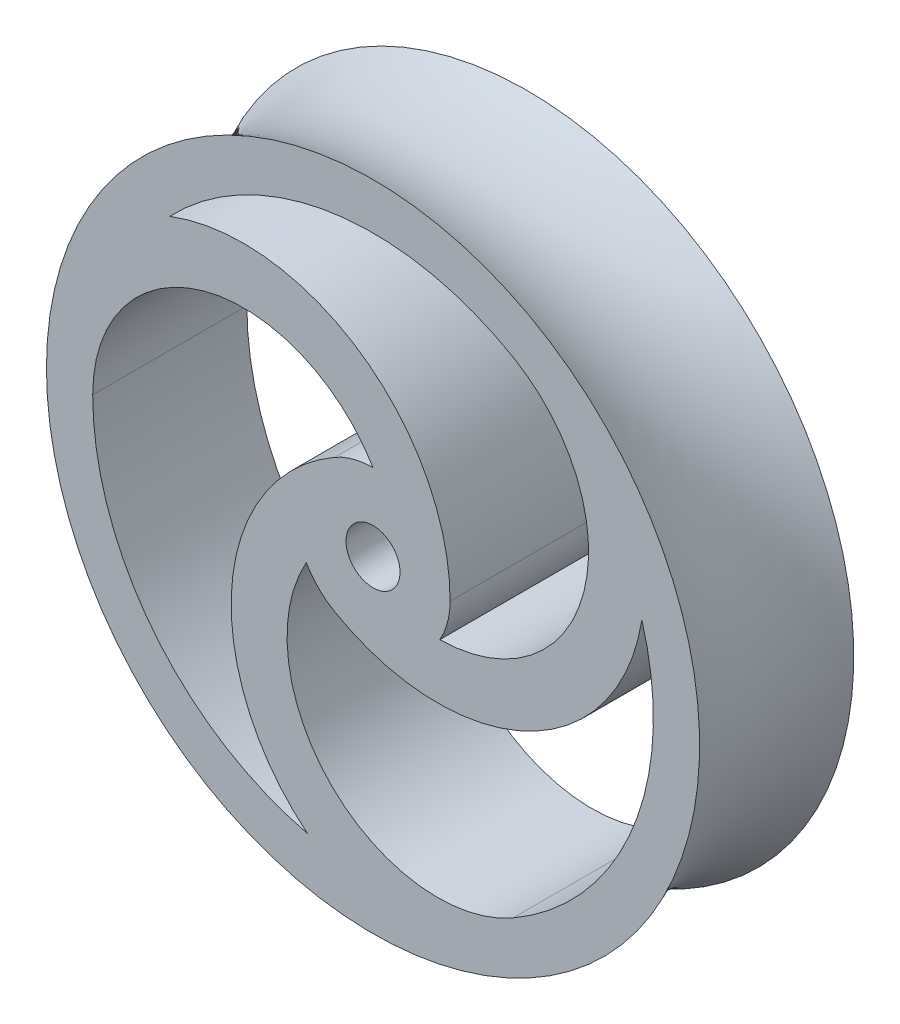
SolidWorks part; units mm, degrees
ref_plane "Front Plane" through (0, 0, 0) normal (0, 0, 1) x (1, 0, 0)
ref_plane "Top Plane" through (0, 0, 0) normal (0, 1, 0) x (1, 0, 0)
ref_plane "Right Plane" through (0, 0, 0) normal (1, 0, 0) x (0, 0, -1)
sketch "Sketch2" plane through (0, 0, 0) normal (0, 1, 0) x (1, 0, 0)
  line L0 (0, 5) -> (0, -5)
  line L1 (0, 5) -> (21.1839, 5)
  line L2 (0, -5) -> (21.1839, -5)
  line L3 (0, 0) -> (20, 0) construction
  arc A0 (21.1839, 5) -> (21.1839, -5) centre (31.15, 0) ccw
  point P4 (0, 0)
  point P9 (26.8135, 5)
  point P10 (26.8135, -5)
  point P11 (20, 0)
  point P12 (27.961, 5)
  dimension "D3" = 11.15
  dimension "D1" = 10
  dimension "D2" = 20
revolve "Revolve1" add sketch "Sketch2" angle 360 about L0
sketch "Sketch3" plane through (0, 0, -5) normal (0, 0, -1) x (-1, 0, 0)
  line L0 (0, 0) -> (0, 21.1839) construction
  line L1 (0, 0) -> (18.1839, 0) construction
  circle A0 centre (0, 0) radius 1.75
  circle A1 centre (0, 0) radius 18.1839 construction
  circle A2 centre (0, 0) radius 21.1839 construction
  arc A3 (-5, 0) -> (13.1839, 12.5236) centre (8.4045, 0) cw construction
  arc A4 (0, 5) -> (18.1839, 0) centre (8.4045, 0) cw construction
  arc A5 (13.1839, 12.5236) -> (18.1839, 0) centre (0, 0) cw construction
  circle A6 centre (0, 0) radius 5 construction
  arc A7 (-5, 0) -> (0, 5) centre (0, 0) cw construction
  arc A8 (4.3301, -2.5) -> (-9.092, -15.7477) centre (-4.2023, -7.2786) cw construction
  arc A9 (2.5, 4.3301) -> (4.3301, -2.5) centre (0, 0) cw construction
  arc A10 (2.5, 4.3301) -> (4.2537, -17.6794) centre (-4.2023, -7.2786) cw construction
  arc A11 (4.2537, -17.6794) -> (-9.092, -15.7477) centre (0, 0) cw construction
  arc A12 (-4.3301, -2.5) -> (-9.092, 15.7477) centre (-4.2023, 7.2786) cw construction
  arc A13 (2.5, -4.3301) -> (-4.3301, -2.5) centre (0, 0) cw construction
  arc A14 (2.5, -4.3301) -> (-17.4377, 5.1558) centre (-4.2023, 7.2786) cw construction
  arc A15 (-17.4377, 5.1558) -> (-9.092, 15.7477) centre (0, 0) cw construction
  arc A16 (0, 5) -> (18.1839, 0) centre (8.4045, 0) cw
  arc A17 (18.1839, 0) -> (4.2537, -17.6794) centre (0, 0) cw
  arc A18 (2.5, 4.3301) -> (4.2537, -17.6794) centre (-4.2023, -7.2786) cw
  arc A19 (0, 5) -> (2.5, 4.3301) centre (0, 0) cw
  arc A20 (4.3301, -2.5) -> (2.5, -4.3301) centre (0, 0) cw
  arc A21 (4.3301, -2.5) -> (-9.092, -15.7477) centre (-4.2023, -7.2786) cw
  arc A22 (-9.092, -15.7477) -> (-17.4377, 5.1558) centre (0, 0) cw
  arc A23 (2.5, -4.3301) -> (-17.4377, 5.1558) centre (-4.2023, 7.2786) cw
  arc A24 (-4.3301, -2.5) -> (-5, 0) centre (0, 0) cw
  arc A25 (-4.3301, -2.5) -> (-9.092, 15.7477) centre (-4.2023, 7.2786) cw
  arc A26 (-9.092, 15.7477) -> (13.1839, 12.5236) centre (0, 0) cw
  arc A27 (-5, 0) -> (13.1839, 12.5236) centre (8.4045, 0) cw
  circle A28 centre (0, 0) radius 21.1839 construction
  point P26 (0, 0)
  point P45 (0, 0)
  point P48 (0, 0)
  dimension "D1" = 3.5
  dimension "D2" = 10
  dimension "D5" = 3
  dimension "D3" = 3
  dimension "D4" = 3
extrude "Cut-Extrude1" cut sketch "Sketch3" against normal through all
